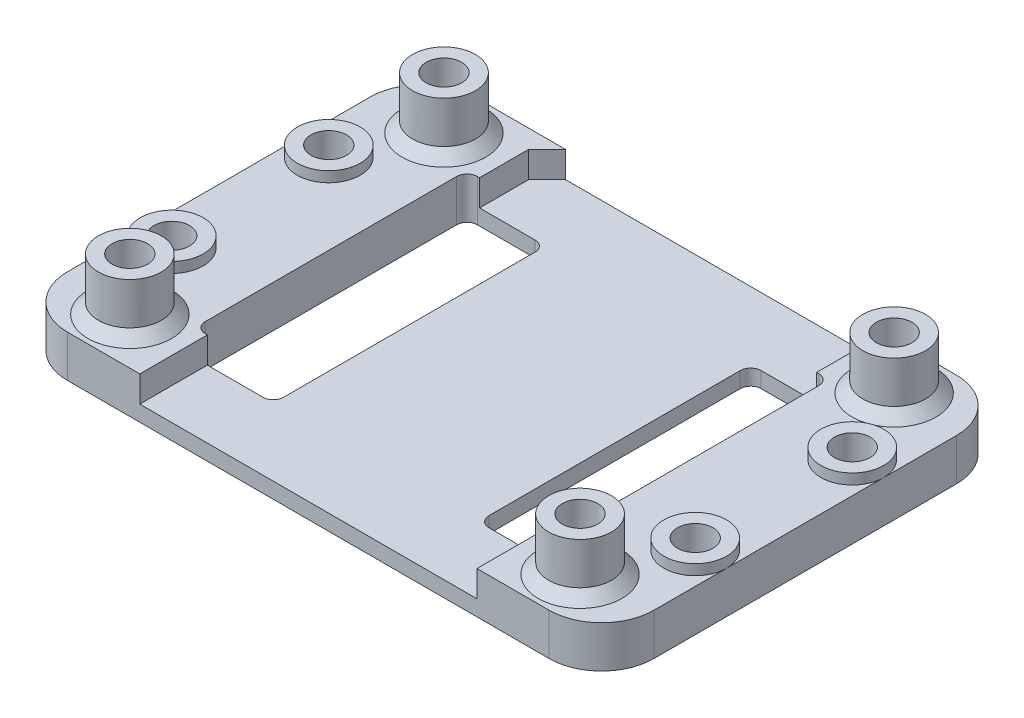
SolidWorks part; units mm, degrees
ref_plane "Front Plane" through (0, 0, 0) normal (0, 0, 1) x (1, 0, 0)
ref_plane "Top Plane" through (0, 0, 0) normal (0, 1, 0) x (1, 0, 0)
ref_plane "Right Plane" through (0, 0, 0) normal (1, 0, 0) x (0, 0, -1)
sketch "Sketch1" plane through (0, 0, 0) normal (0, 1, 0) x (1, 0, 0)
  line L0 (-15.6, 17.4701) -> (-13.6201, 19.45)
  line L1 (-13.6201, 19.45) -> (13.6201, 19.45)
  line L2 (-15.6, 17.4701) -> (-15.6, -19.45)
  line L3 (-15.6, -19.45) -> (15.6, -19.45)
  line L4 (15.6, 17.4701) -> (15.6, -19.45)
  line L5 (-14.7188, 18.3513) -> (15.6, -19.45) construction
  line L6 (-15.6, -19.45) -> (14.7188, 18.3513) construction
  line L7 (-13.6201, 19.45) -> (13.6201, 19.45)
  line L8 (13.6201, 19.45) -> (15.6, 17.4701)
  point P0 (0, 0)
  dimension "D1" = 31.2
  dimension "D2" = 38.9
  dimension "D3" = 45
  dimension "D4" = 2.8
  dimension "D5" = 2.8
  dimension "D6" = 19.45
  dimension "D7" = 15.6
sketch "Sketch2" plane through (0, 0, 0) normal (0, 1, 0) x (1, 0, 0)
  line L1 (-25, 7.5) -> (25, 7.5) construction
  line L2 (-25, 7.5) -> (-25, -7.5) construction
  line L3 (-25, -7.5) -> (25, -7.5) construction
  line L4 (25, 7.5) -> (25, -7.5) construction
  line L5 (-25, 7.5) -> (25, -7.5) construction
  line L6 (-25, -7.5) -> (25, 7.5) construction
  circle A0 centre (-25, 7.5) radius 1.7
  circle A1 centre (-25, -7.5) radius 1.7
  circle A2 centre (25, -7.5) radius 1.7
  circle A3 centre (25, 7.5) radius 1.7
  circle A4 centre (-25, 7.5) radius 3
  circle A5 centre (-25, -7.5) radius 3
  circle A6 centre (25, -7.5) radius 3
  circle A7 centre (25, 7.5) radius 3
  point P0 (0, 0)
  dimension "D3" = 3.4
  dimension "D4" = 6
  dimension "D1" = 50
  dimension "D2" = 15
extrude "Boss-Extrude1" add sketch "Sketch2" along normal blind 5
sketch "Sketch3" plane through (0, 0, 0) normal (0, 1, 0) x (1, 0, 0)
  line L0 (-13.6201, 19.45) -> (13.6201, 19.45) construction
  line L1 (-28, -19.45) -> (28, -19.45)
  line L2 (-28, -19.45) -> (-28, 19.45)
  line L3 (-28, 19.45) -> (28, 19.45)
  line L4 (28, -19.45) -> (28, 19.45)
  line L5 (-28, -19.45) -> (28, 19.45) construction
  line L6 (-28, 19.45) -> (28, -19.45) construction
  circle A0 centre (-25, 7.5) radius 3 construction
  circle A1 centre (-25, 7.5) radius 1.7 construction
  circle A2 centre (-25, 7.5) radius 1.7
  circle A3 centre (25, 7.5) radius 1.7 construction
  circle A4 centre (25, -7.5) radius 1.7 construction
  circle A5 centre (-25, -7.5) radius 1.7 construction
  circle A6 centre (25, 7.5) radius 1.7
  circle A7 centre (25, -7.5) radius 1.7
  circle A8 centre (-25, -7.5) radius 1.7
  point P0 (0, 0)
extrude "Boss-Extrude2" add sketch "Sketch3" along normal blind 4
fillet "Fillet1" radius 5 4 edges at (-28, 2, -19.45) (28, 2, -19.45) (28, 2, 19.45) (-28, 2, 19.45)
extrude "Cut-Extrude2" cut sketch "Sketch1" against normal blind 2.5 from surface contours L8 L1 L0 L2 L3 L4 region at (0, 0, 0.0609) starting at face at (0, 4, -0.75)
sketch "Sketch4" plane through (0, 4, 0) normal (0, 1, 0) x (1, 0, 0)
  line L41 (-16.1, -19.95) -> (16.1, -19.95)
  line L42 (13.8272, 19.95) -> (-13.8272, 19.95)
  line L43 (16.1, -19.95) -> (16.1, 17.6772)
  line L44 (16.1, 17.6772) -> (13.8272, 19.95)
  line L45 (-16.1, 17.6772) -> (-16.1, -19.95)
  line L46 (-13.8272, 19.95) -> (-16.1, 17.6772)
  line L47 (-16.1, -19.95) -> (16.1, -19.95)
  line L48 (13.8272, 19.95) -> (-13.8272, 19.95)
  line L49 (16.1, -19.95) -> (16.1, 17.6772)
  line L50 (16.1, 17.6772) -> (13.8272, 19.95)
  line L51 (-16.1, 17.6772) -> (-16.1, -19.95)
  line L52 (-13.8272, 19.95) -> (-16.1, 17.6772)
  dimension "D1" = 0.5
extrude "Cut-Extrude3" cut sketch "Sketch4" against normal up to surface (2.5 mm away) up to face at (0, 1.5, -5.8234)
sketch "Sketch5" plane through (0, 4, 0) normal (0, 1, 0) x (1, 0, 0)
  line L1 (-21.5, 15) -> (21.5, 15) construction
  line L2 (-21.5, 15) -> (-21.5, -15) construction
  line L3 (-21.5, -15) -> (21.5, -15) construction
  line L4 (21.5, 15) -> (21.5, -15) construction
  line L5 (-21.5, 15) -> (21.5, -15) construction
  line L6 (-21.5, -15) -> (21.5, 15) construction
  circle A0 centre (-21.5, 15) radius 1.7
  circle A1 centre (21.5, 15) radius 1.7
  circle A2 centre (21.5, -15) radius 1.7
  circle A3 centre (-21.5, -15) radius 1.7
  circle A4 centre (-21.5, 15) radius 3
  circle A5 centre (21.5, 15) radius 3
  circle A6 centre (21.5, -15) radius 3
  circle A7 centre (-21.5, -15) radius 3
  point P0 (0, 0)
  dimension "D1" = 3.4
  dimension "D4" = 6
  dimension "D2" = 43
  dimension "D3" = 30
extrude "Boss-Extrude3" add sketch "Sketch5" along normal blind 5
extrude "Cut-Extrude4" cut sketch "Sketch5<2>" against normal through all contours A0 | A3 | A2 | A1
sketch "Sketch5<2>" plane through (0, 4, 0) normal (0, 1, 0) x (1, 0, 0) same geometry as "Sketch5"
sketch "Sketch6" plane through (0, 0, 0) normal (0, -1, 0) x (1, 0, 0)
  line L1 (-19.97, 12.35) -> (-18.44, 15)
  line L2 (-18.44, 15) -> (-19.97, 17.65)
  line L3 (-19.97, 17.65) -> (-23.03, 17.65)
  line L4 (-23.03, 17.65) -> (-24.56, 15)
  line L5 (-24.56, 15) -> (-23.03, 12.35)
  line L6 (-23.03, 12.35) -> (-19.97, 12.35)
  line L7 (23.03, 12.35) -> (24.56, 15)
  line L8 (24.56, 15) -> (23.03, 17.65)
  line L9 (23.03, 17.65) -> (19.97, 17.65)
  line L10 (19.97, 17.65) -> (18.44, 15)
  line L11 (18.44, 15) -> (19.97, 12.35)
  line L12 (19.97, 12.35) -> (23.03, 12.35)
  line L13 (24.56, -15) -> (23.03, -12.35)
  line L14 (23.03, -12.35) -> (19.97, -12.35)
  line L15 (19.97, -12.35) -> (18.44, -15)
  line L16 (18.44, -15) -> (19.97, -17.65)
  line L17 (19.97, -17.65) -> (23.03, -17.65)
  line L18 (23.03, -17.65) -> (24.56, -15)
  line L19 (-18.44, -15) -> (-19.97, -12.35)
  line L20 (-19.97, -12.35) -> (-23.03, -12.35)
  line L21 (-23.03, -12.35) -> (-24.56, -15)
  line L22 (-24.56, -15) -> (-23.03, -17.65)
  line L23 (-23.03, -17.65) -> (-19.97, -17.65)
  line L24 (-19.97, -17.65) -> (-18.44, -15)
  circle A0 centre (-21.5, 15) radius 2.65 construction
  circle A1 centre (21.5, 15) radius 2.65 construction
  circle A2 centre (21.5, -15) radius 2.65 construction
  circle A3 centre (-21.5, -15) radius 2.65 construction
  point P28 (0, 0)
  dimension "D1" = 5.3
extrude "Cut-Extrude5" cut sketch "Sketch6" against normal blind 2.5
chamfer "Chamfer1" distance 1 angle 45 1 edges at (-21.5, 4, 12)
chamfer "Chamfer2" distance 1 angle 45 3 edges at (21.5, 4, 12) (21.5, 4, -18) (-21.5, 4, -18)
sketch "Sketch7" plane through (0, 1.5, 0) normal (0, 1, 0) x (1, 0, 0)
  line L1 (-9.8, -13) -> (-17.3, -13)
  line L2 (-9.8, -13) -> (-9.8, 13)
  line L3 (-9.8, 13) -> (-17.3, 13)
  line L4 (-17.3, -13) -> (-17.3, 13)
  line L5 (-9.8, -13) -> (-17.3, 13) construction
  line L6 (-9.8, 13) -> (-17.3, -13) construction
  line L8 (9.8, -13) -> (17.3, -13)
  line L9 (9.8, -13) -> (9.8, 13)
  line L10 (9.8, 13) -> (17.3, 13)
  line L11 (17.3, -13) -> (17.3, 13)
  line L12 (9.8, -13) -> (17.3, 13) construction
  line L13 (9.8, 13) -> (17.3, -13) construction
  point P0 (-13.55, 0)
  point P7 (13.55, 0)
  point P14 (0, 0)
  dimension "D1" = 7.5
  dimension "D2" = 26
extrude "Cut-Extrude6" cut sketch "Sketch7" against normal through all both and the other way through all
fillet "Fillet3" radius 1 8 edges at (-17.3, 2, 13) (-9.8, 0.75, 13) (-17.3, 2, -13) (-9.8, 0.75, -13) (9.8, 0.75, 13) (17.3, 2, 13) (9.8, 0.75, -13) (17.3, 2, -13)
sketch "Sketch8" plane through (0, 0, 0) normal (0, 1, 0) x (1, 0, 0)
  line L0 (-5.6, -23.5) -> (5.6, -23.5) construction
  line L1 (-5.6, -23.5) -> (-5.6, 23.5) construction
  line L2 (-5.6, 23.5) -> (5.6, 23.5) construction
  line L3 (5.6, -23.5) -> (5.6, 23.5) construction
  line L4 (-5.6, -23.5) -> (5.6, 23.5) construction
  line L5 (-5.6, 23.5) -> (5.6, -23.5) construction
  circle A0 centre (-5.6, 23.5) radius 0.8
  circle A1 centre (5.6, 23.5) radius 0.8
  circle A2 centre (5.6, -23.5) radius 0.8
  circle A3 centre (-5.6, -23.5) radius 0.8
  circle A4 centre (-5.6, 23.5) radius 2
  circle A5 centre (5.6, 23.5) radius 2
  circle A6 centre (-5.6, -23.5) radius 2
  circle A7 centre (5.6, -23.5) radius 2
  point P0 (0, 0)
  point P13 (0, 0)
  dimension "D1" = 1.6
  dimension "D2" = 4
  dimension "D3" = 11.2
  dimension "D4" = 47
